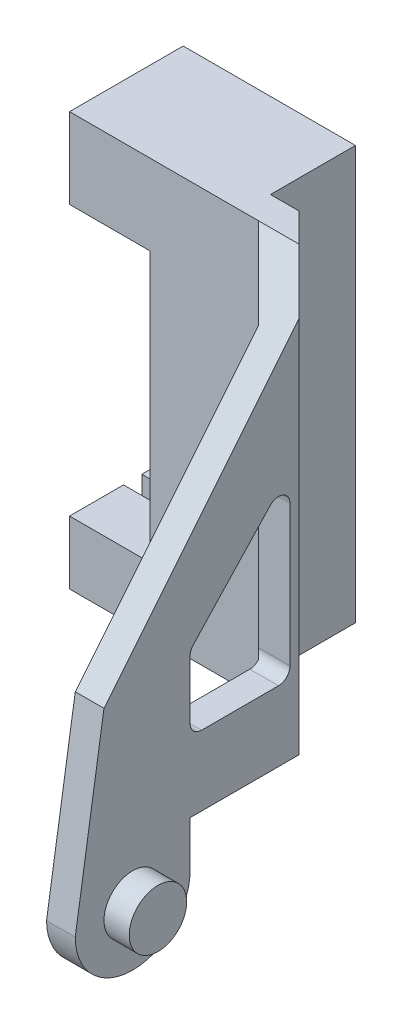
SolidWorks part; units mm, degrees
ref_plane "Płaszczyzna przednia" through (0, 0, 0) normal (0, 0, 1) x (1, 0, 0)
ref_plane "Płaszczyzna górna" through (0, 0, 0) normal (0, 1, 0) x (1, 0, 0)
ref_plane "Płaszczyzna prawa" through (0, 0, 0) normal (1, 0, 0) x (0, 0, -1)
sketch "Szkic1" plane through (0, 0, 0) normal (1, 0, 0) x (0, 0, -1)
  line L0 (0, 0) -> (0, 36)
  line L1 (0, 36) -> (-9.9, 36)
  line L2 (-9.9, 36) -> (-9.9, 0)
  line L3 (-9.9, 0) -> (0, 0)
  dimension "D1" = 36
  dimension "D2" = 9.9
extrude "Dodanie-wyciągnięcie1" add sketch "Szkic1" along normal blind 15
sketch "Szkic2" plane through (15, 0, 0) normal (1, 0, 0) x (0, 0, -1)
  line L0 (-9.9, 36) -> (-7.4, 36)
  line L1 (0, 36) -> (-9.9, 36) construction
  line L2 (-7.4, 36) -> (-7.4, 0)
  line L3 (-9.9, 0) -> (0, 0) construction
  line L4 (-7.4, 0) -> (-21.9, 0)
  line L5 (-21.9, 0) -> (-21.9, -4)
  line L6 (-31.9, -4) -> (-29.4, 12)
  line L7 (-29.4, 12) -> (-9.9, 36)
  line L8 (-9.9, 36) -> (-9.9, 0) construction
  circle A0 centre (-26.9, -4) radius 5
  line M5 (-9.9, 0) -> (0, 0)
  line M7 (0, 36) -> (-9.9, 36)
  line M8 (-9.9, 36) -> (-9.9, 0)
  dimension "D3" = 10
  dimension "D1" = 2.5
  dimension "D2" = 12
  dimension "D4" = 4
  dimension "D5" = 22
  dimension "D6" = 12
  dimension "D7" = 4
extrude "Dodanie-wyciągnięcie2" add sketch "Szkic2" along normal blind 7.5 contours A0 L6 | A0 L5 L4 L7 L6 M8 | L2 M7 M8 M5 region at (15, 12.791, 18.2866) region at (15, 18, 8.65) region at (15, -4.0006, 26.8961)
sketch "Szkic3" plane through (0, 36, 0) normal (0, 1, 0) x (1, 0, 0)
  line L0 (15, -7.4) -> (17.5, -7.4)
  line L1 (22.5, -7.4) -> (15, -7.4) construction
  line L2 (17.5, -7.4) -> (22.5, -12.4)
  line L3 (22.5, -29.4) -> (22.5, -9.9) construction
  line L4 (22.5, -12.4) -> (22.5, -7.4)
  line L5 (22.5, -7.4) -> (17.5, -7.4)
  line L6 (15, -9.9) -> (16.4645, -9.9)
  line L7 (22.5, -9.9) -> (15, -9.9) construction
  line L8 (16.4645, -9.9) -> (20, -13.4355)
  line L9 (20, -13.4355) -> (20, -32.7453)
  line L10 (20, -32.7453) -> (7.9993, -32.7453)
  line L11 (7.9993, -32.7453) -> (15, -9.9)
  point P15 (22.5, -19.65)
  line M7 (15, -9.9) -> (22.5, -9.9)
  line M8 (22.5, -9.9) -> (22.5, -7.4)
  line M9 (22.5, -7.4) -> (15, -7.4)
  dimension "D1" = 2.5
  dimension "D2" = 45
  dimension "D3" = 2.5
  dimension "D4" = 2.5
extrude "Wytnij-wyciągnięcie1" cut sketch "Szkic3" against normal blind 57.5 contours L11 L10 L9 L8 M7 | L2 M9 M7 M8 | L2 L4 M7 region at (20.5556, 36, 8.5111) region at (15.3994, 36, 23.2834) region at (21.6667, 36, 10.7333)
sketch "Szkic4" plane through (0, 0, 9.9) normal (0, 0, 1) x (1, 0, 0)
  line L0 (0, 29) -> (7, 29)
  line L1 (0, 36) -> (0, 0) construction
  line L2 (7, 29) -> (7, 5.5)
  line L3 (7, 5.5) -> (0, 5.5)
  line L4 (0, 5.5) -> (0, 29)
  line L5 (16.4645, 36) -> (0, 36) construction
  dimension "D1" = 7
  dimension "D2" = 23.5
  dimension "D3" = 7
extrude "Wytnij-wyciągnięcie2" cut sketch "Szkic4" against normal blind 57.5
sketch "Szkic5" plane through (22.5, 0, 0) normal (1, 0, 0) x (0, 0, -1)
  arc A0 (-31.9, -4) -> (-21.9, -4) centre (-26.9, -4) ccw construction
  arc A1 (-31.9, -4) -> (-21.9, -4) centre (-26.9, -4) ccw
  circle A2 centre (-26.9, -4) radius 2.5
  dimension "D1" = 5
extrude "Dodanie-wyciągnięcie3" add sketch "Szkic5" along normal blind 2.2 contours A2 region at (22.5, -4, 26.9)
sketch "Szkic6" plane through (22.5, 0, 0) normal (1, 0, 0) x (0, 0, -1)
  line L0 (-13.2, 6.1) -> (-13.2, 21.9)
  line L1 (-13.2, 21.9) -> (-21.9, 12.6)
  line L2 (-21.9, 12.6) -> (-21.9, 6.1)
  line L3 (-21.9, 6.1) -> (-13.2, 6.1)
  line L4 (0, 0) -> (0, 36) construction
  line L5 (-12.4, 0) -> (-21.9, 0) construction
  dimension "D1" = 13.2
  dimension "D2" = 8.7
  dimension "D3" = 6.5
  dimension "D4" = 6.1
  dimension "D5" = 15.8
extrude "Wytnij-wyciągnięcie3" cut sketch "Szkic6" against normal blind 10
fillet "Zaokrąglenie1" radius 1 4 edges at (21.1322, 21.9, 13.2) (21.25, 12.6, 21.9) (21.25, 6.1, 21.9) (21.1322, 6.1, 13.2)
sketch "Szkic7" plane through (0, 0, 0) normal (-1, 0, 0) x (0, 0, 1)
  line L0 (5.2, 31.4) -> (5.2, 29) construction
  line L1 (5.2, 31.4) -> (5.2, 33.4) construction
  line L2 (3.6, 33.4) -> (5.2, 33.4) construction
  line L3 (3.6, 33.4) -> (3.6, 31.4) construction
  line L4 (3.6, 29) -> (3.6, 31.4) construction
  line L5 (5.2, 31.4) -> (5.2, 29)
  line L6 (5.2, 31.4) -> (5.2, 33.4)
  line L7 (3.6, 33.4) -> (5.2, 33.4)
  line L8 (3.6, 33.4) -> (3.6, 31.4)
  line L9 (3.6, 29) -> (3.6, 31.4)
  line L10 (3.6, 3.1) -> (3.6, 5.5) construction
  line L11 (5.2, 5.5) -> (5.2, 3.1) construction
  line L12 (5.2, 1.1) -> (5.2, 3.1) construction
  line L13 (3.6, 3.1) -> (3.6, 1.1) construction
  line L14 (5.2, 1.1) -> (3.6, 1.1) construction
  line L15 (3.6, 3.1) -> (3.6, 5.5)
  line L16 (5.2, 5.5) -> (5.2, 3.1)
  line L17 (5.2, 1.1) -> (5.2, 3.1)
  line L18 (3.6, 3.1) -> (3.6, 1.1)
  line L19 (5.2, 1.1) -> (3.6, 1.1)
  line L20 (3.6, 5.5) -> (5.2, 5.5)
  line L21 (3.6, 29) -> (5.2, 29)
extrude "Wytnij-wyciągnięcie4" cut sketch "Szkic7" against normal blind 7
